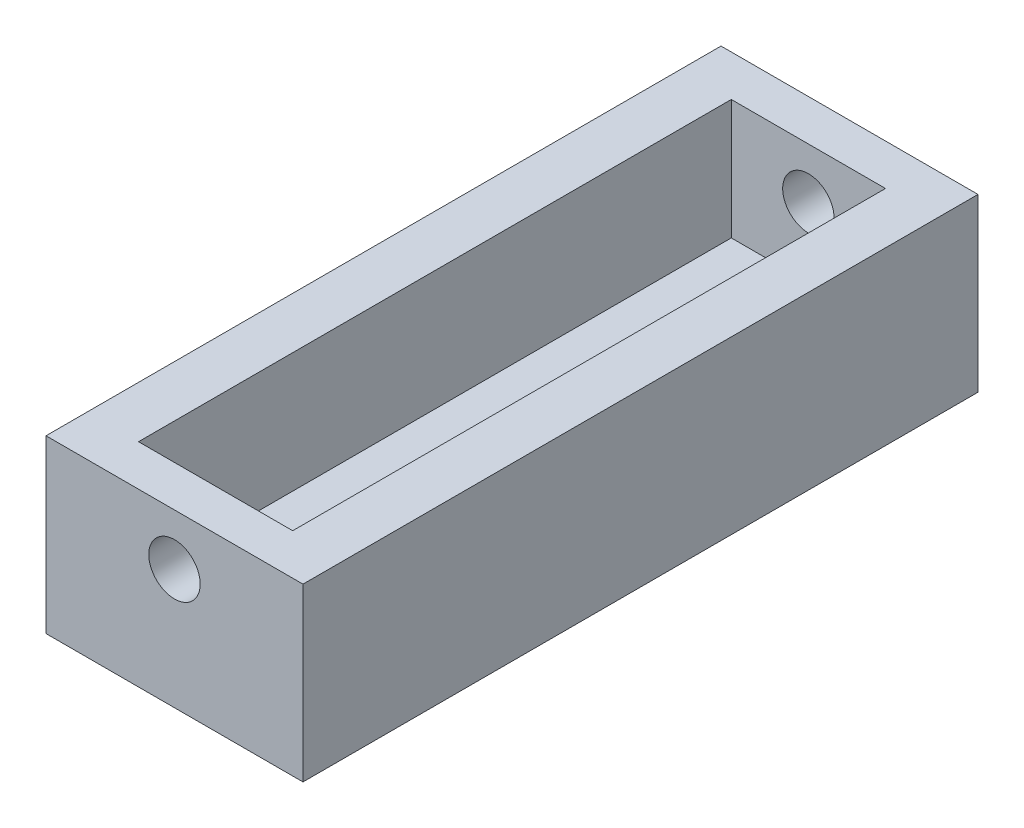
SolidWorks part; units mm, degrees
material "ABS"
ref_plane "Front Plane" through (0, 0, 0) normal (0, 0, 1) x (1, 0, 0)
ref_plane "Top Plane" through (0, 0, 0) normal (0, 1, 0) x (1, 0, 0)
ref_plane "Right Plane" through (0, 0, 0) normal (1, 0, 0) x (0, 0, -1)
sketch "Sketch1" plane through (0, 0, 0) normal (0, 0, 1) x (1, 0, 0)
  line L0 (-3.75, 0) -> (3.75, 0) construction
  line L1 (3.75, 0) -> (3.75, 5)
  line L2 (3.75, 5) -> (2.25, 5)
  line L3 (2.25, 5) -> (2.25, 1.5)
  line L4 (-2.25, 1.5) -> (2.25, 1.5) construction
  line L5 (-2.25, 1.5) -> (-2.25, 5)
  line L6 (-2.25, 5) -> (-3.75, 5)
  line L7 (-3.75, 5) -> (-3.75, 0)
  line L8 (0, 0) -> (0, 1.5) construction
  line L9 (-2.25, 1.5) -> (-0.6, 1.5)
  line L10 (-0.6, 1.5) -> (-0.6, 0)
  line L11 (2.25, 1.5) -> (0.6, 1.5)
  line L12 (0.6, 1.5) -> (0.6, 0)
  line L13 (0.6, 0) -> (3.75, 0)
  line L14 (-0.6, 0) -> (-3.75, 0)
  dimension "D1" = 1.5
  dimension "D2" = 7.5
  dimension "D7" = 4.5
  dimension "D5" = 0.6
  dimension "D3" = 5
  dimension "D4" = 1.5
  dimension "D6" = 0.6
extrude "body" add sketch "Sketch1" along normal blind 17.3
sketch "Sketch2" plane through (0, 0, 0) normal (0, 0, 1) x (1, 0, 0)
  line L0 (-3.75, 5) -> (3.75, 5)
  line L1 (3.75, 5) -> (3.75, 0)
  line L2 (3.75, 0) -> (-3.75, 0)
  line L3 (-3.75, 0) -> (-3.75, 5)
extrude "end" add sketch "Sketch2" against normal blind 1.2 contours L3 | L3 L2 L1 L0 region at (0, 2.5, 0)
extrude "end1" add sketch "Sketch2<4>" along normal blind 1.2 from offset 17.3
sketch "Sketch2<4>" plane through (0, 0, 0) normal (0, 0, 1) x (1, 0, 0) same geometry as "Sketch2"
sketch "Sketch3" plane through (0, 0, 18.5) normal (0, 0, 1) x (1, 0, 0)
  line L0 (0, 5) -> (0, 0) construction
  line L1 (3.75, 5) -> (-3.75, 5) construction
  line L2 (-3.75, 2.5) -> (3.75, 2.5) construction
  line L3 (-3.75, 5) -> (-3.75, 0) construction
  line L4 (3.75, 0) -> (3.75, 5) construction
  line L5 (-3.75, 3.5) -> (3.75, 3.5) construction
  circle A0 centre (0, 3.5) radius 0.75
  dimension "D1" = 1.5
  dimension "D2" = 1
extrude "tendon hole" cut sketch "Sketch3" against normal up to surface (19.7 mm away) up to face at (0, 2.5, -1.2)
